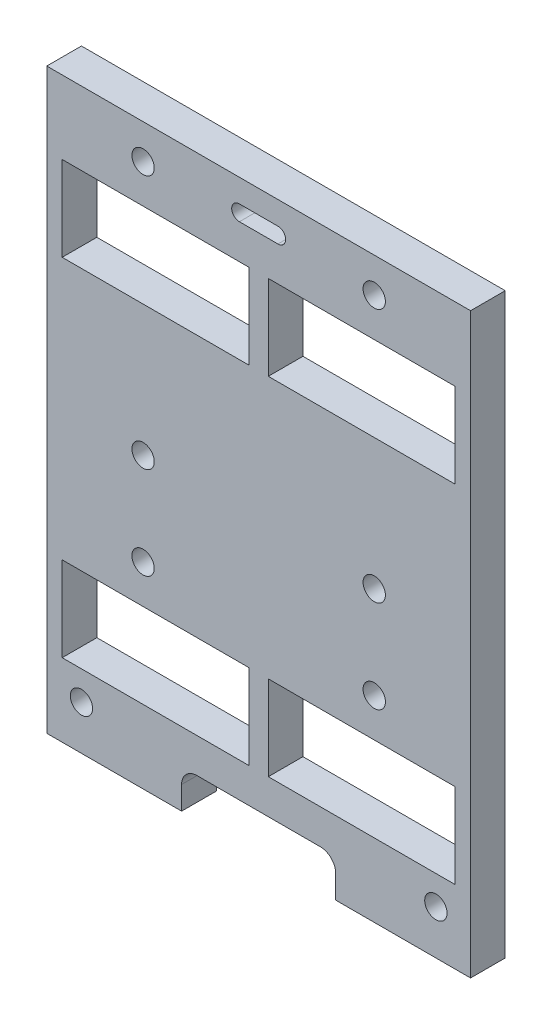
SolidWorks part; units mm, degrees
ref_plane "Front Plane" through (0, 0, 0) normal (0, 0, 1) x (1, 0, 0)
ref_plane "Top Plane" through (0, 0, 0) normal (0, 1, 0) x (1, 0, 0)
ref_plane "Right Plane" through (0, 0, 0) normal (1, 0, 0) x (0, 0, -1)
sketch "Sketch1" plane through (0, 0, 0) normal (0, 0, 1) x (1, 0, 0)
  line L0 (0, -37.5) -> (0, 37.5) construction
  line L1 (-27.5, -37.5) -> (27.5, -37.5)
  line L2 (-27.5, -37.5) -> (-27.5, 37.5)
  line L3 (-27.5, 37.5) -> (27.5, 37.5)
  line L4 (27.5, -37.5) -> (27.5, 37.5)
  line L5 (-27.5, -37.5) -> (27.5, 37.5) construction
  line L6 (-27.5, 37.5) -> (27.5, -37.5) construction
  line L7 (-27.5, 0) -> (27.5, 0) construction
  line L8 (-27.5, 22.5) -> (27.5, 22.5) construction
  line L9 (25.5, 17) -> (1.25, 28) construction
  line L10 (-25.5, 28) -> (-1.25, 28)
  line L11 (-25.5, 28) -> (-25.5, 17)
  line L12 (-25.5, 17) -> (-1.25, 17)
  line L13 (-1.25, 28) -> (-1.25, 17)
  line L14 (-25.5, 28) -> (-1.25, 17) construction
  line L15 (-25.5, 17) -> (-1.25, 28) construction
  line L16 (25.5, 28) -> (1.25, 17) construction
  line L17 (1.25, 28) -> (1.25, 17)
  line L18 (25.5, 17) -> (1.25, 17)
  line L19 (25.5, 28) -> (25.5, 17)
  line L20 (25.5, 28) -> (1.25, 28)
  line L21 (25.5, -28) -> (1.25, -17) construction
  line L22 (-25.5, -17) -> (-1.25, -28) construction
  line L23 (-25.5, -28) -> (-1.25, -17) construction
  line L24 (25.5, -17) -> (1.25, -28) construction
  line L25 (25.5, -28) -> (1.25, -28)
  line L26 (25.5, -28) -> (25.5, -17)
  line L27 (25.5, -17) -> (1.25, -17)
  line L28 (1.25, -28) -> (1.25, -17)
  line L29 (-1.25, -28) -> (-1.25, -17)
  line L30 (-25.5, -17) -> (-1.25, -17)
  line L31 (-25.5, -28) -> (-25.5, -17)
  line L32 (-25.5, -28) -> (-1.25, -28)
  point P0 (0, 0)
  point P12 (-13.375, 22.5)
  point P21 (13.375, 22.5)
  point P30 (13.375, -22.5)
  point P31 (-13.375, -22.5)
  dimension "D1" = 55
  dimension "D2" = 75
  dimension "D3" = 22.5
  dimension "D4" = 24.25
  dimension "D5" = 11
  dimension "D6" = 1.25
extrude "Boss-Extrude1" add sketch "Sketch1" along normal blind 4.5
sketch "Sketch2" plane through (0, 0, 4.5) normal (0, 0, 1) x (1, 0, 0)
  line L0 (0, -37.5) -> (0, 37.5) construction
  line L1 (-27.5, -37.5) -> (27.5, -37.5) construction
  line L2 (27.5, 37.5) -> (-27.5, 37.5) construction
  line L3 (-27.5, 0) -> (27.5, 0) construction
  line L4 (-27.5, 37.5) -> (-27.5, -37.5) construction
  line L5 (27.5, -37.5) -> (27.5, 37.5) construction
  line L6 (-15, 0) -> (15, 0) construction
  circle A0 centre (-15, 33) radius 1.45
  circle A1 centre (15, 33) radius 1.45
  circle A2 centre (15, 0) radius 1.45
  circle A3 centre (-15, 0) radius 1.45
  dimension "D1" = 2.9
  dimension "D7" = 2.9
  dimension "D8" = 2.9
  dimension "D2" = 15
  dimension "D3" = 33
  dimension "D4" = 30
  dimension "D5" = 15
  dimension "D6" = 0
extrude "screwHoles" cut sketch "Sketch2" against normal through all
sketch "Sketch3" plane through (0, 0, 4.5) normal (0, 0, 1) x (1, 0, 0)
  line L0 (-27.5, 9) -> (26.0486, 9) construction
  line L1 (-27.5, 37.5) -> (-27.5, -37.5) construction
  line L3 (0, 37.5) -> (0, -37.5) construction
  line L4 (27.5, 37.5) -> (-27.5, 37.5) construction
  line L5 (-27.5, -37.5) -> (27.5, -37.5) construction
  line L6 (18.95, 6.8) -> (9.05, 11.2) construction
  line L7 (-18.95, 11.2) -> (-9.05, 11.2)
  line L8 (-18.95, 11.2) -> (-18.95, 6.8)
  line L9 (-18.95, 6.8) -> (-9.05, 6.8)
  line L10 (-9.05, 11.2) -> (-9.05, 6.8)
  line L11 (-18.95, 11.2) -> (-9.05, 6.8) construction
  line L12 (-18.95, 6.8) -> (-9.05, 11.2) construction
  line L13 (18.95, 11.2) -> (9.05, 6.8) construction
  line L14 (9.05, 11.2) -> (9.05, 6.8)
  line L15 (18.95, 6.8) -> (9.05, 6.8)
  line L16 (18.95, 11.2) -> (18.95, 6.8)
  line L17 (18.95, 11.2) -> (9.05, 11.2)
  line L18 (-27.5, 37.5) -> (-27.5, -37.5) construction
  point P2 (-27.5, 0)
  point P12 (-14, 9)
  point P21 (14, 9)
  dimension "D1" = 9.9
  dimension "D3" = 14
  dimension "D4" = 9
extrude "BeltClamp" [suppressed] cut sketch "Sketch3" against normal through all
sketch "Sketch4" plane through (0, 0, 4.5) normal (0, 0, 1) x (1, 0, 0)
  line L0 (-27.5, 0) -> (27.5, 0) construction
  line L1 (-27.5, 37.5) -> (-27.5, -37.5) construction
  line L2 (27.5, -37.5) -> (27.5, 37.5) construction
  line L4 (-4.85, 2.175) -> (4.85, 2.175)
  line L5 (-4.85, 2.175) -> (-4.85, -2.175)
  line L6 (-4.85, -2.175) -> (4.85, -2.175)
  line L7 (4.85, 2.175) -> (4.85, -2.175)
  line L8 (-4.85, 2.175) -> (4.85, -2.175) construction
  line L9 (-4.85, -2.175) -> (4.85, 2.175) construction
  circle A0 centre (-15, 0) radius 1.45 construction
  point P6 (0, 0)
  dimension "D2" = 4.35
  dimension "D3" = 0
extrude "mountingPlateTab" [suppressed] cut sketch "Sketch4" against normal through all
sketch "Sketch5" plane through (0, 0, 4.5) normal (0, 0, 1) x (1, 0, 0)
  line L0 (-27.5, -9.75) -> (27.5, -9.75) construction
  line L1 (-27.5, 37.5) -> (-27.5, -37.5) construction
  line L2 (27.5, -37.5) -> (27.5, 37.5) construction
  line L4 (0, -37.5) -> (0, 37.5) construction
  line L5 (-27.5, -37.5) -> (27.5, -37.5) construction
  line L6 (27.5, 37.5) -> (-27.5, 37.5) construction
  line L7 (-20.825, -14.6) -> (-25.175, -4.9) construction
  line L8 (20.825, -4.9) -> (25.175, -4.9)
  line L9 (20.825, -4.9) -> (20.825, -14.6)
  line L10 (20.825, -14.6) -> (25.175, -14.6)
  line L11 (25.175, -4.9) -> (25.175, -14.6)
  line L12 (20.825, -4.9) -> (25.175, -14.6) construction
  line L13 (20.825, -14.6) -> (25.175, -4.9) construction
  line L14 (-20.825, -4.9) -> (-25.175, -14.6) construction
  line L15 (-25.175, -4.9) -> (-25.175, -14.6)
  line L16 (-20.825, -14.6) -> (-25.175, -14.6)
  line L17 (-20.825, -4.9) -> (-20.825, -14.6)
  line L18 (-20.825, -4.9) -> (-25.175, -4.9)
  line L19 (23, -9.75) -> (23, -37.5) construction
  line L20 (-23, -9.75) -> (-23, -37.5) construction
  circle A0 centre (23, -31.75) radius 1.45
  circle A1 centre (-23, -31.75) radius 1.45
  point P15 (23, -9.75)
  point P24 (-23, -9.75)
  dimension "D5" = 2.9
  dimension "D2" = 9.7
  dimension "D3" = 4.35
  dimension "D4" = 23
  dimension "D6" = 22
  dimension "D1" = 9.75
extrude "BraceTabs" cut sketch "Sketch5" against normal through all
sketch "Sketch6" [suppressed] plane through (0, 0, 4.5) normal (0, 0, 1) x (1, 0, 0)
  line L0 (-25.175, -9.75) -> (25.175, -9.75) construction
  line L1 (-25.175, -4.9) -> (-25.175, -14.6) construction
  line L2 (25.175, -14.6) -> (25.175, -4.9) construction
  line L3 (0, -2.175) -> (0, -37.5) construction
  line L4 (-4.85, -2.175) -> (4.85, -2.175) construction
  line L5 (-27.5, -37.5) -> (27.5, -37.5) construction
  line L6 (23, -14.6) -> (23, -4.9) construction
  line L7 (20.825, -14.6) -> (25.175, -14.6) construction
  line L8 (25.175, -4.9) -> (20.825, -4.9) construction
  line L9 (20.825, -4.9) -> (20.825, -14.6) construction
  line L10 (19.825, -15.6) -> (26.175, -15.6)
  line L11 (19.825, -15.6) -> (19.825, -3.9)
  line L12 (19.825, -3.9) -> (26.175, -3.9)
  line L13 (26.175, -15.6) -> (26.175, -3.9)
  line L14 (19.825, -15.6) -> (26.175, -3.9) construction
  line L15 (19.825, -3.9) -> (26.175, -15.6) construction
  line L16 (-19.825, -3.9) -> (-26.175, -15.6) construction
  line L17 (-19.825, -15.6) -> (-26.175, -3.9) construction
  line L18 (-23, -14.6) -> (-23, -4.9) construction
  line L19 (-26.175, -15.6) -> (-26.175, -3.9)
  line L20 (-19.825, -3.9) -> (-26.175, -3.9)
  line L21 (-19.825, -15.6) -> (-19.825, -3.9)
  line L22 (-19.825, -15.6) -> (-26.175, -15.6)
  circle A0 centre (23, -9.75) radius 1.45
  circle A1 centre (-23, -9.75) radius 1.45
  point P18 (23, -9.75)
  dimension "D3" = 2.9
  dimension "D1" = 1
  dimension "D2" = 1
extrude "FrontToRear1" [suppressed] add sketch "Sketch6" against normal up to surface (4.5 mm away) up to face at (-24.45, -31.75, 0)
sketch "Sketch7" [suppressed] plane through (0, 0, 4.5) normal (0, 0, 1) x (1, 0, 0)
  line L0 (4.85, 2.175) -> (-4.85, 2.175) construction
  line L1 (-20, -3.175) -> (20, -3.175)
  line L2 (-20, -3.175) -> (-20, 3.175)
  line L3 (-20, 3.175) -> (20, 3.175)
  line L4 (20, -3.175) -> (20, 3.175)
  line L5 (-20, -3.175) -> (20, 3.175) construction
  line L6 (-20, 3.175) -> (20, -3.175) construction
  circle A0 centre (15, 0) radius 1.45 construction
  point P0 (0, 0)
  dimension "D1" = 1
  dimension "D2" = 5
extrude "FrontToRear2" [suppressed] add sketch "Sketch7" against normal through all
sketch "Sketch8" plane through (0, 0, 4.5) normal (0, 0, 1) x (1, 0, 0)
  line L0 (-27.5, -12) -> (27.5, -12) construction
  line L1 (-27.5, 37.5) -> (-27.5, -37.5) construction
  line L2 (27.5, -37.5) -> (27.5, 37.5) construction
  line L3 (0, -37.5) -> (0, 0) construction
  line L4 (-27.5, -37.5) -> (27.5, -37.5) construction
  circle A0 centre (-15, -12) radius 1.45
  circle A1 centre (15, -12) radius 1.45
  dimension "D2" = 2.9
  dimension "D1" = 12
  dimension "D3" = 15
extrude "ExpansionScrewholes" cut sketch "Sketch8" against normal through all
sketch "Sketch12" plane through (0, 0, 4.5) normal (0, 0, 1) x (1, 0, 0)
  line L0 (0, 37.5) -> (0, 0) construction
  line L1 (27.5, 37.5) -> (-27.5, 37.5) construction
  line L2 (-2.5, 33.5) -> (2.5, 33.5) construction
  line L3 (-2.5, 34.5) -> (2.5, 34.5)
  line L4 (-2.5, 32.5) -> (2.5, 32.5)
  arc A0 (-2.5, 34.5) -> (-2.5, 32.5) centre (-2.5, 33.5) ccw
  arc A1 (2.5, 32.5) -> (2.5, 34.5) centre (2.5, 33.5) ccw
  point P7 (0, 33.5)
  dimension "D1" = 3
  dimension "D2" = 2
  dimension "D3" = 5
extrude "CableTieSlot" cut sketch "Sketch12" against normal through all
sketch "Sketch11" plane through (0, 0, 4.5) normal (0, 0, 1) x (1, 0, 0)
  line L0 (13.5615, -8.6) -> (27.5, -8.6) construction
  line L1 (27.5, -37.5) -> (27.5, 37.5) construction
  line L2 (0, 37.5) -> (0, -37.5) construction
  line L3 (36.5, -14.6) -> (18.5, -14.6)
  line L4 (36.5, -14.6) -> (36.5, -2.6)
  line L5 (36.5, -2.6) -> (18.5, -2.6)
  line L6 (18.5, -14.6) -> (18.5, -2.6)
  line L7 (36.5, -14.6) -> (18.5, -2.6) construction
  line L8 (36.5, -2.6) -> (18.5, -14.6) construction
  line L11 (-36.5, -2.6) -> (-18.5, -14.6) construction
  line L12 (-36.5, -14.6) -> (-18.5, -2.6) construction
  line L13 (-18.5, -14.6) -> (-18.5, -2.6)
  line L14 (-36.5, -2.6) -> (-18.5, -2.6)
  line L15 (-36.5, -14.6) -> (-36.5, -2.6)
  line L16 (-36.5, -14.6) -> (-18.5, -14.6)
  line L17 (36.5, -2.6) -> (18.5, -14.6) construction
  line L18 (20.825, -14.6) -> (25.175, -14.6) construction
  line L19 (27.5, 37.5) -> (-27.5, 37.5) construction
  line L20 (-27.5, -37.5) -> (27.5, -37.5) construction
  dimension "D1" = 9
  dimension "D2" = 12
  dimension "D3" = 0
extrude "Cut-Extrude2" [suppressed] cut sketch "Sketch11" against normal through all
sketch "Sketch10" [suppressed] plane through (0, 0, 4.5) normal (0, 0, 1) x (1, 0, 0)
  line L0 (4.7446, 1) -> (27.5, 1) construction
  line L1 (-4.85, 0) -> (4.85, 0) construction
  line L2 (27.5, -37.5) -> (27.5, 37.5) construction
  line L3 (0, 2.175) -> (0, -2.175) construction
  line L4 (36.5, 4) -> (18.5, 4)
  line L5 (36.5, 4) -> (36.5, -2)
  line L6 (36.5, -2) -> (18.5, -2)
  line L7 (18.5, 4) -> (18.5, -2)
  line L8 (36.5, 4) -> (18.5, -2) construction
  line L9 (36.5, -2) -> (18.5, 4) construction
  line L10 (4.85, 2.175) -> (-4.85, 2.175) construction
  line L11 (-4.85, -2.175) -> (4.85, -2.175) construction
  line L12 (-36.5, -2) -> (-18.5, 4) construction
  line L13 (-36.5, 4) -> (-18.5, -2) construction
  line L14 (-4.7446, 1) -> (-27.5, 1) construction
  line L15 (-18.5, 4) -> (-18.5, -2)
  line L16 (-36.5, -2) -> (-18.5, -2)
  line L17 (-36.5, 4) -> (-36.5, -2)
  line L18 (-36.5, 4) -> (-18.5, 4)
  line L19 (36.5, -2) -> (18.5, 4) construction
  line L20 (-4.85, 2.175) -> (-4.85, -2.175) construction
  line L21 (4.85, -2.175) -> (4.85, 2.175) construction
  dimension "D1" = 6
  dimension "D2" = 9
  dimension "D3" = 1
extrude "CableTieSlots" [suppressed] cut sketch "Sketch10" against normal through all
sketch "Sketch9" plane through (0, 0, 4.5) normal (0, 0, 1) x (1, 0, 0)
  line L0 (-27.5, -37.5) -> (27.5, -37.5) construction
  line L5 (-10, -42.5) -> (10, -42.5)
  line L6 (-10, -42.5) -> (-10, -34.5)
  line L7 (-8, -32.5) -> (8, -32.5)
  line L8 (10, -42.5) -> (10, -34.5)
  line L9 (-10, -42.5) -> (10, -32.5) construction
  line L10 (-10, -32.5) -> (10, -42.5) construction
  arc A0 (8, -32.5) -> (10, -34.5) centre (8, -34.5) cw
  arc A1 (-10, -34.5) -> (-8, -32.5) centre (-8, -34.5) cw
  point P9 (0, -37.5)
  line M42 (-27.5, -37.5) -> (27.5, -37.5)
  dimension "D3" = 2
  dimension "D1" = 20
  dimension "D2" = 5
extrude "RearFanSlot" cut sketch "Sketch9" against normal through all contours A1 L6 L8 A0 L7 M42 | L5 L8 L6 M42
sketch "Sketch13" [suppressed] plane through (0, 0, 4.5) normal (0, 0, 1) x (1, 0, 0)
  line L1 (-7, -2.85) -> (7, -2.85)
  line L2 (-7, -2.85) -> (-7, -11.85)
  line L3 (-7, -11.85) -> (7, -11.85)
  line L4 (7, -2.85) -> (7, -11.85)
  line L5 (-7, -2.85) -> (7, -11.85) construction
  line L6 (-7, -11.85) -> (7, -2.85) construction
  line L9 (0, 37.5) -> (0, -7.35) construction
  line L10 (-18.5, -2.85) -> (-27.5, -2.85) construction
  line L11 (27.5, 37.5) -> (-27.5, 37.5) construction
  line L13 (-27.5, -14.85) -> (-18.5, -14.85) construction
  point P0 (0, -7.35)
  dimension "D1" = 3
  dimension "D2" = 0
  dimension "D3" = 7
extrude "Cut-Extrude3" [suppressed] cut sketch "Sketch13" against normal through all
sketch "Sketch14" plane through (0, 0, 4.5) normal (0, 0, 1) x (1, 0, 0)
  line L0 (25.175, -4.9) -> (20.825, -4.9) construction
  line L1 (25.175, -4.9) -> (20.825, -4.9)
  line L2 (25.175, -4.9) -> (25.175, -14.6)
  line L3 (25.175, -14.6) -> (20.825, -14.6)
  line L4 (20.825, -4.9) -> (20.825, -14.6)
  line L5 (25.175, -14.6) -> (25.175, -4.9) construction
  line L6 (0, 0) -> (0, -6.835) construction
  line L7 (-20.825, -4.9) -> (-20.825, -14.6)
  line L8 (-25.175, -14.6) -> (-20.825, -14.6)
  line L9 (-25.175, -4.9) -> (-25.175, -14.6)
  line L10 (-25.175, -4.9) -> (-20.825, -4.9)
extrude "Boss-Extrude2" add sketch "Sketch14" against normal through all
equation "\"X-ROD-SPACING\"=45"
equation "\"Y-ROD-SPACING\"=75"
equation "\"Z-ROD-SPACING\"=17.5"
equation "\"Y-BED-OFFSET\"=2"
equation "\"Y-BED-ROD-INSET\"=3.5"
equation "\"Y-BED-SCREW-SPACING\"=209"
equation "\"Y-BED-SCREW-CUTOUT-SLOT-HEIGHT\"=2.5"
equation "\"T-SLOT-NUT-FILLET-RADIUS\"=0.5"
equation "\"T-SLOT-SCREW-SHAFT-RADIUS\"=1.55"
equation "\"T-SLOT-SCREW-SHAFT-CUTOUT-LENGTH\"=11"
equation "\"T-SLOT-NUT-DEPTH\"=3.5"
equation "\"T-SLOT-NUT-WIDTH\"=2.85"
equation "\"T-SLOT-NUT-END-DISTANCE\"=8"
equation "\"ACRYLIC-THICKNESS\"=10"
equation "\"ACRYLIC-THICKNESS2\"=4.5"
equation "\"ACRYLIC-TAB-CUTOUT-SIZE\"=\"ACRYLIC-THICKNESS\"+\"ACRYLIC-TAB-TOLERANCE\"*2"
equation "\"ACRYLIC-TAB-WIDTH\"=\"ACRYLIC-THICKNESS\""
equation "\"ACRYLIC-M3-HOLE\"=2.9"
equation "\"SMOOTHROD-CAP-SCREW-DISTANCE\"=20"
equation "\"FRAME-WIDTH-INNER\"=370"
equation "\"NEMA17-HOLE-SPACING\"=31"
equation "\"NEMA17-CENTRAL-CUTOUT\"=22.5"
equation "\"Z-BRACKET-REACH\"=57"
equation "\"Z-ROD-INSET\"=13.5"
equation "\"TOP-BRACKET-SPACING\"=40"
equation "\"SMOOTHROD-X-LENGTH\"=350"
equation "\"SMOOTHROD-Y-LENGTH\"=350"
equation "\"SMOOTHROD-Z-LENGTH\"=350"
equation "\"SMOOTHROD-TIGHTENING-HEADROOM\"=.25"
equation "\"LEADSCREW-Z-LENGTH\"=300"
equation "\"SCREW-LENGTH-FRAME\"=\"ACRYLIC-THICKNESS\" + 10"
equation "\"SCREW-LENGTH-MOTOR\"=\"ACRYLIC-THICKNESS\" + 5"
equation "\"SCREW-HEAD-RADIUS\"=6"
equation "\"PRINTED-X-SMOOTHROD-DIAMETER\"=8.8"
equation "\"PRINTED-X-SMOOTHROD-CUTOUT\"=10"
equation "\"PRINTED-X-BASE-HEIGHT\"=10"
equation "\"PRINTED-LM8UU-CUTOUT-SIZE\"=15.5"
equation "\"PRINTED-LM8UU-CUTOUT-LENGTH\"=24.5"
equation "\"PRINTED-X-IDLER-HEIGHT\"=16"
equation "\"PSU-MOUNTING-WIDTH\"=95"
equation "\"PSU-MOUNTING-HEIGHT\"=177"
equation "\"Y-BELT-TO-ROD-DISTANCE\"=20"
equation "\"SPOOL-HOLDER-ROD-SPACING\"=150"
equation "\"D3@Sketch1\"=\"X-ROD-SPACING\"/2"
equation "\"D4@Sketch1\"=\"ACRYLIC-X-CARRIAGE-LM8UU-CUTOUT-WIDTH\""
equation "\"D1@Boss-Extrude1\"=\"ACRYLIC-THICKNESS2\""
equation "\"D1@Sketch2\"=\"ACRYLIC-M3-HOLE\""
equation "\"D1@Sketch3\"=\"ACRYLIC-TAB-CUTOUT-SIZE\""
equation "\"D2@Sketch3\"=\"ACRYLIC-THICKNESS2\"+\"ACRYLIC-TAB-TOLERANCE\"*2"
equation "\"ACRYLIC-X-CARRIAGE-WIDTH\"=55"
equation "\"ACRYLIC-X-CARRIAGE-HEIGHT\"=75"
equation "\"D1@Sketch1\"=\"ACRYLIC-X-CARRIAGE-WIDTH\""
equation "\"D2@Sketch1\"=\"ACRYLIC-X-CARRIAGE-HEIGHT\""
equation "\"ACRYLIC-X-CARRIAGE-CENTER-TAB-SPACING\"=14"
equation "\"D3@Sketch3\"=\"ACRYLIC-X-CARRIAGE-CENTER-TAB-SPACING\""
equation "\"SCREW-LENGTH-EXTRUDER\"=28"
equation "\"ACRYLIC-X-CARRIAGE-SCREW-SPACING-X\"=15"
equation "\"ACRYLIC-X-CARRIAGE-SCREW-SPACING-Y\"=33"
equation "\"D2@Sketch2\"=\"ACRYLIC-X-CARRIAGE-SCREW-SPACING-X\""
equation "\"D3@Sketch2\"=\"ACRYLIC-X-CARRIAGE-SCREW-SPACING-Y\""
equation "\"D1@Sketch4\"=\"ACRYLIC-TAB-WIDTH\"-\"KERF\"*4"
equation "\"D2@Sketch4\"=\"ACRYLIC-THICKNESS2\"-\"KERF\"*2"
equation "\"D2@Sketch5\"=\"ACRYLIC-TAB-WIDTH\"-\"KERF\"*4"
equation "\"D3@Sketch5\"=\"ACRYLIC-THICKNESS2\"-\"KERF\"*2"
equation "\"ACRYLIC-X-CARRIAGE-EXTRUDER-SHELF-DEPTH\"=\"ACRYLIC-X-CARRIAGE-EXTRUDER-OFFSET\" + 28"
equation "\"ACRYLIC-X-CARRIAGE-EXTRUDER-BRACE-SPACING\"=23"
equation "\"D4@Sketch5\"=\"ACRYLIC-X-CARRIAGE-EXTRUDER-BRACE-SPACING\""
equation "\"D4@Sketch2\"=\"ACRYLIC-X-CARRIAGE-SCREW-SPACING-X\"*2"
equation "\"D5@Sketch2\"=\"ACRYLIC-X-CARRIAGE-SCREW-SPACING-X\""
equation "\"D7@Sketch2\"=\"ACRYLIC-M3-HOLE\""
equation "\"D8@Sketch2\"=\"ACRYLIC-M3-HOLE\""
equation "\"ACRYLIC-X-CARRIAGE-LM8UU-CUTOUT-WIDTH\"=24.25"
equation "\"ACRYLIC-TAB-TOLERANCE\"=-.05"
equation "\"ACRYLIC-X-CARRIAGE-EXTRUDER-OFFSET\"=26"
equation "\"ACRYLIC-X-CARRIAGE-EXTRUDER-ANGLE\"=90"
equation "\"ACRYLIC-X-CARRIAGE-EXTRUDER-BRACE-TAB-OFFSET\"=20"
equation "\"ACRYLIC-X-CARRIAGE-EXTRUDER-BRACE-HEIGHT\"=35"
equation "\"ACRYLIC-X-CARRIAGE-EXTRUDER-BRACE-SCREW-SPACING\"=22"
equation "\"D5@Sketch5\"=\"ACRYLIC-M3-HOLE\""
equation "\"D3@Sketch6\"=\"ACRYLIC-M3-HOLE\""
equation "\"ACRYLIC-X-CARRIAGE-LM8UU-CUTOUT-HEIGHT\"=11.0"
equation "\"ACRYLIC-X-CARRIAGE-DUAL-WIDTH-MULTIPLIER\"=1.65"
equation "\"ACRYLIC-X-CARRIAGE-DUAL-HOTEND-SPACING\"=42"
equation "\"ACRYLIC-X-CARRIAGE-DUAL-WIDTH\"=75"
equation "\"ACRYLIC-X-CARRIAGE-DUAL-HOTEND-SEPARATION\"=36"
equation "\"ACRYLIC-X-CARRIAGE-DUAL-MOUNT-PLATE-DEPTH\"=75"
equation "\"ACRYLIC-X-CARRIAGE-DUAL-MOUNT-BRACE-WIDTH\"=33"
equation "\"ACRYLIC-X-CARRIAGE-DUAL-MOUNT-SCREW-WIDTH\"=40"
equation "\"D5@Sketch1\"=\"ACRYLIC-X-CARRIAGE-LM8UU-CUTOUT-HEIGHT\""
equation "\"D2@Sketch8\"=\"ACRYLIC-M3-HOLE\""
equation "\"D1@Sketch5\"=\"ACRYLIC-THICKNESS2\"/2 + 7.5"
equation "\"KERF\"=0.075"
equation "\"PRINTED-M3-HOLE\"=3.5"
equation "\"PRINTED-M3-NUT-AF\"=6.25"
equation "\"ACRYLIC-X-CARRIAGE-DUAL-FAN-OFFSET\"=52"
equation "\"ACRYLIC-X-CARRIAGE-DUAL-FAN-HEIGHT\"=20"
equation "\"BLOWER-FAN-WIDTH\"=15"
